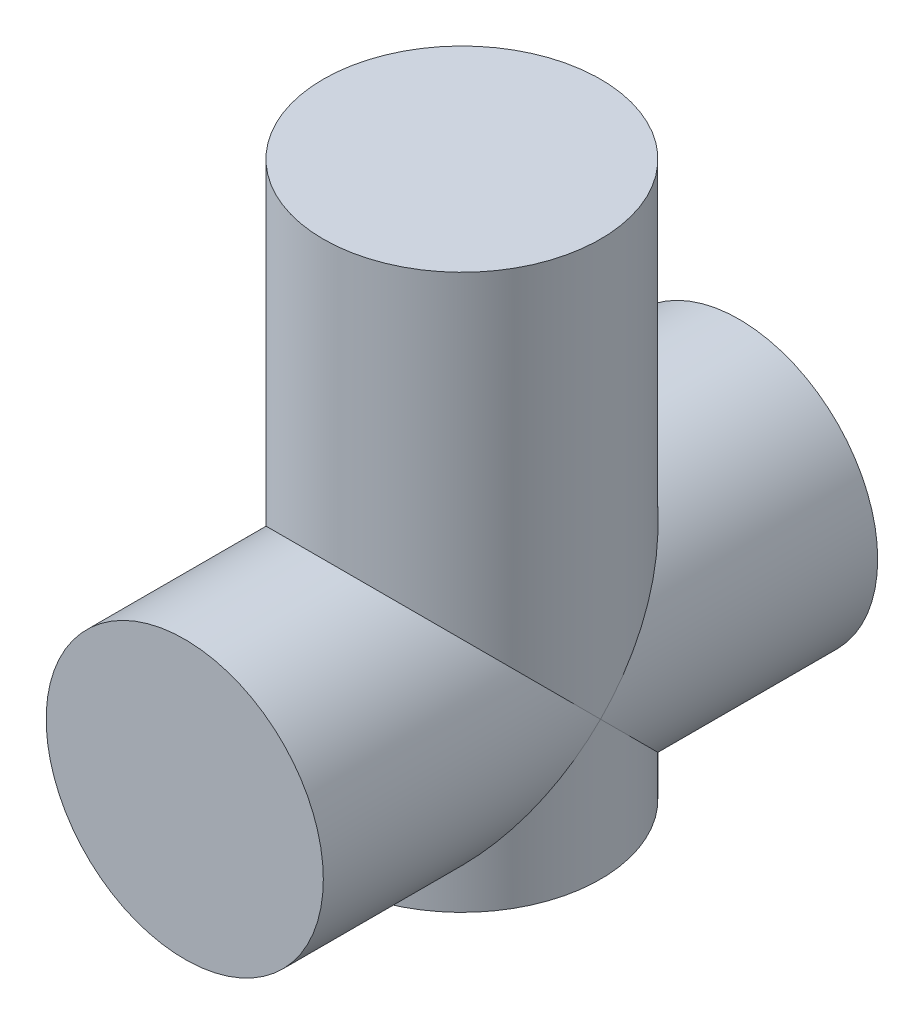
SolidWorks part; units mm, degrees
ref_plane "Front Plane" through (0, 0, 0) normal (0, 0, 1) x (1, 0, 0)
ref_plane "Top Plane" through (0, 0, 0) normal (0, 1, 0) x (1, 0, 0)
ref_plane "Right Plane" through (0, 0, 0) normal (1, 0, 0) x (0, 0, -1)
sketch "Sketch1" plane through (0, 0, 0) normal (0, 1, 0) x (1, 0, 0)
  circle A0 centre (0, 0) radius 25
extrude "Boss-Extrude1" add sketch "Sketch1" along normal blind 100 contours A0
sketch "Sketch2" plane through (0, 0, 0) normal (0, 0, 1) x (1, 0, 0)
  circle A0 centre (0, 25) radius 25
extrude "Boss-Extrude2" add sketch "Sketch2" along normal blind 50 and the other way blind 50
